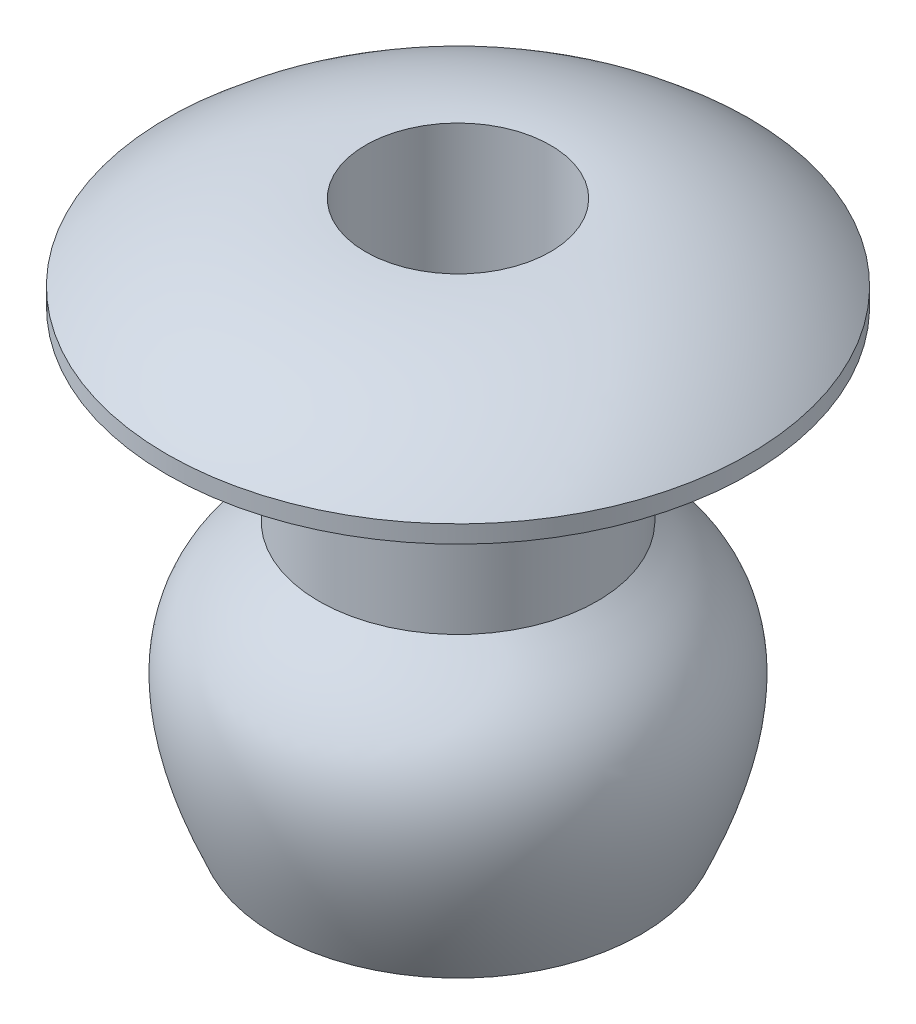
SolidWorks part; units mm, degrees
material "Alloy Steel"
ref_plane "Front Plane" through (0, 0, 0) normal (0, 0, 1) x (1, 0, 0)
ref_plane "Top Plane" through (0, 0, 0) normal (0, 1, 0) x (1, 0, 0)
ref_plane "Right Plane" through (0, 0, 0) normal (1, 0, 0) x (0, 0, -1)
sketch "Sketch1" plane through (0, 0, 0) normal (1, 0, 0) x (0, 0, -1)
  line L0 (0, 0) -> (0, -3.175) construction
  line L1 (-2.3813, 0) -> (-2.3812, -3.175)
  line L2 (-2.3813, 0) -> (-4.9784, 0)
  line L3 (-4.9784, 0) -> (-4.9784, 0.3)
  line L4 (-1.5813, 1.6002) -> (-1.5812, -3.5315)
  line L5 (-2.4098, -7.735) -> (-3.1312, -7.735)
  line L6 (-1.8464, -3.7699) -> (-1.5812, -3.5315)
  line L7 (-2.4001, -7.4104) -> (-2.3184, -7.5944)
  arc A0 (-1.5813, 1.6002) -> (-4.9784, 0.3) centre (-1.5812, -3.4879) ccw
  arc A1 (-2.4098, -7.735) -> (-2.3184, -7.5944) centre (-2.4098, -7.635) ccw
  spline S0 degree 3 poles (-3.1312, -7.735) (-4.4816, -4.6934) (-3.2852, -3.9878) (-2.3812, -3.175) knots 0 0 0 0 0.915818 0.915818 0.915818 0.915818
  spline S1 degree 1 poles (-2.4001, -7.4104) (-1.8464, -3.7699) knots 0 0 1 1 construction
  spline S2 degree 3 poles (-2.4001, -7.4104) (-2.4735, -7.245) (-2.6187, -6.8931) (-2.8155, -6.3129) (-2.9423, -5.7177) (-2.9434, -5.2211) (-2.8341, -4.775) (-2.6024, -4.4496) (-2.2124, -4.0868) (-1.9625, -3.8744) (-1.8464, -3.7699) knots 0 0 0 0 0.057239 0.114477 0.228955 0.343432 0.457909 0.686864 0.801341 0.915818 0.915818 0.915818 0.915818
  dimension "D12" = 0.1
  dimension "D1" = 3.175
  dimension "D2" = 0.3
  dimension "D3" = 1.6002
  dimension "D4" = 2.3813
  dimension "D5" = 4.9784
  dimension "D6" = 0.8
  dimension "D7" = 0.8
  dimension "D8" = 0.75
  dimension "D9" = 4.56
  dimension "D10" = 2.5
  dimension "D11" = 0.6
revolve "Revolve1" add sketch "Sketch1" angle 360 about L0
